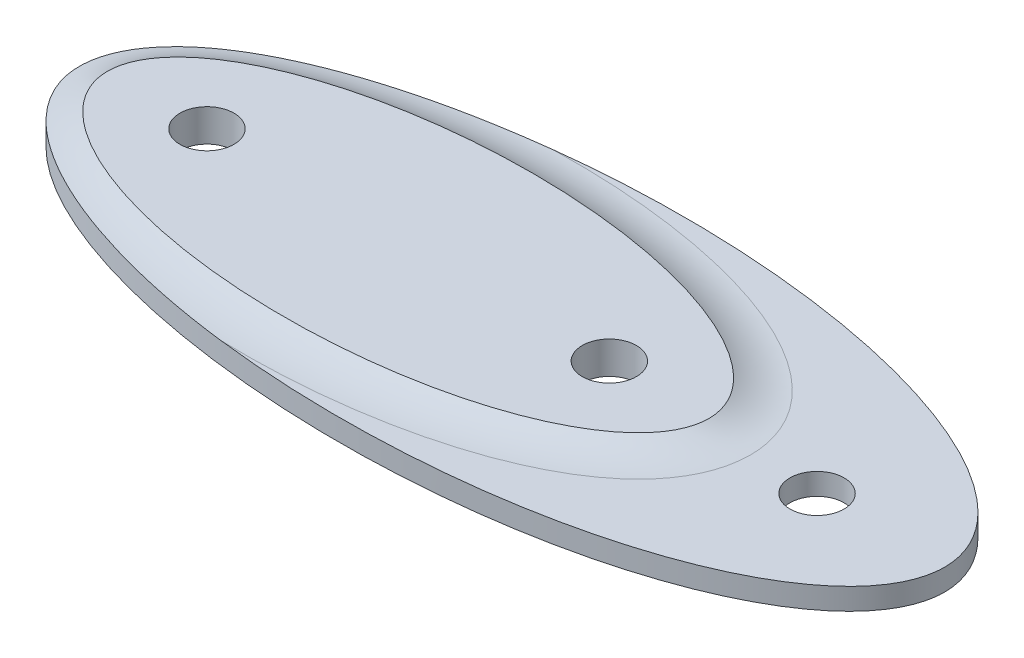
SolidWorks part; units mm, degrees
note: The reader was unsure of these and kept them because the rebuilt part matched: shared geometry of "Sketch1<5>".
ref_plane "Front Plane" through (0, 0, 0) normal (0, 0, 1) x (1, 0, 0)
ref_plane "Top Plane" through (0, 0, 0) normal (0, 1, 0) x (1, 0, 0)
ref_plane "Right Plane" through (0, 0, 0) normal (1, 0, 0) x (0, 0, -1)
sketch "Sketch1" plane through (0, 0, 0) normal (0, 1, 0) x (1, 0, 0)
  line L0 (-95.3563, 14.3465) -> (-48.1123, 14.3465)
  circle A3 centre (-95.3563, 14.3465) radius 3.175
  circle A4 centre (-23.7283, 14.3465) radius 3.175
  circle A5 centre (-48.1123, 14.3465) radius 3.175
  ellipse E0 centre (-59.5423, 14.3465) end of major axis (-110.3423, 14.3465) minor radius 20.32
  ellipse E1 centre (-71.7343, 14.3465) end of major axis (-107.0403, 14.3465) minor radius 14.605
  dimension "D1" = 101.6
  dimension "D4" = 35.814
  dimension "D5" = 47.244
  dimension "D6" = 70.612
  dimension "D2" = 40.64
  dimension "D3" = 35.814
  dimension "D7" = 29.21
extrude "Boss-Extrude1" add sketch "Sketch1" along normal blind 2.54
extrude "Boss-Extrude3" add sketch "Sketch1<5>" along normal blind 3.81
sketch "Sketch1<5>" plane through (0, 0, 0) normal (0, 1, 0) x (1, 0, 0) same geometry as "Sketch1"
fillet "Fillet1" radius 10 1 edges at (-36.4283, 2.54, -14.3465)
